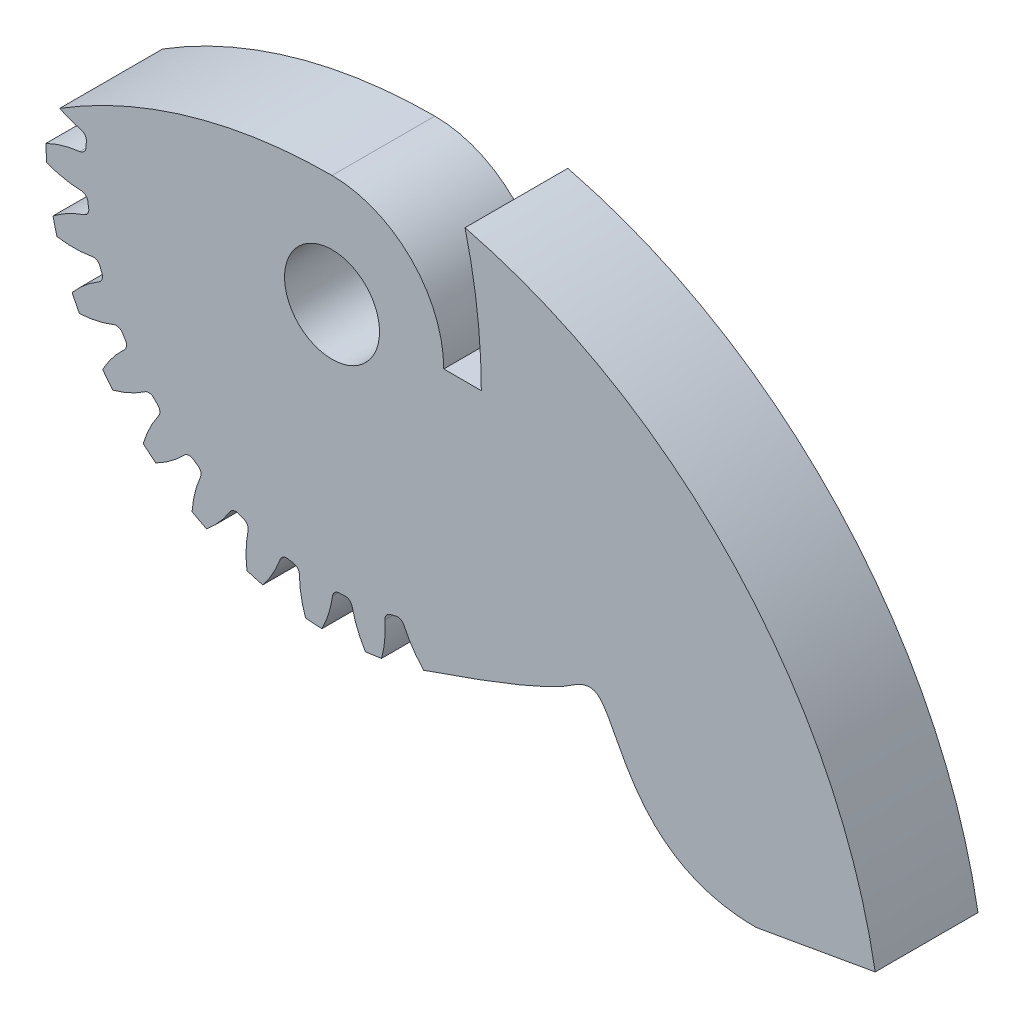
SolidWorks part; units mm, degrees
material "ABS"
ref_plane "Front" through (0, 0, 0) normal (0, 0, 1) x (1, 0, 0)
ref_plane "Top" through (0, 0, 0) normal (0, 1, 0) x (1, 0, 0)
ref_plane "Right" through (0, 0, 0) normal (1, 0, 0) x (0, 0, -1)
sketch "Sketch3" plane through (0, 0, 0) normal (0, 0, 1) x (1, 0, 0)
  circle A0 centre (0, 0) radius 40.64
  dimension "od" = 81.28
extrude "gearBody" add sketch "Sketch3" along normal blind 14.605
sketch "Sketch2" plane through (0, 0, 0) normal (0, 0, 1) x (1, 0, 0)
  line L0 (0, 0) -> (34.0786, 14.1158) construction
  line L1 (45.4751, -11.4855) -> (0, 0) construction
  line L2 (0, 0) -> (36.3143, 0) construction
  line L3 (38.0972, -0.458) -> (37.8451, -4.4001) construction
  line L5 (37.9712, -2.4291) -> (0, 0) construction
  line L7 (0, 0) -> (36.8864, 0) construction
  arc A0 (36.879, -0.7403) -> (36.6727, -3.9649) centre (0, 0) ccw construction
  arc A1 (40.637, 0.4947) -> (40.2427, -5.6687) centre (0, 0) ccw construction
  arc A2 (38.0972, -0.458) -> (37.8451, -4.4001) centre (0, 0) ccw construction
  arc A3 (34.9015, -2.6404) -> (34.9534, -1.8283) centre (0, 0) ccw
  arc A4 (45.4751, -11.4855) -> (35.6466, -3.6712) centre (32.0022, -18.3431) ccw
  arc A5 (45.4751, -11.4855) -> (46.5679, 5.5974) centre (0, 0) ccw
  arc A6 (46.5679, 5.5974) -> (35.8238, -0.9008) centre (34.0786, 14.1158) cw
  arc A7 (34.9534, -1.8283) -> (35.8238, -0.9008) centre (35.9376, -1.8798) cw
  arc A8 (35.6466, -3.6712) -> (34.9015, -2.6404) centre (35.8842, -2.7147) cw
  point P6 (46.5679, 5.5974)
  point P22 (45.4751, -11.4855)
  dimension "baseDia" = 73.7729
  dimension "od" = 81.28
  dimension "pd" = 76.2
  dimension "rd" = 70.0024
  dimension "rFillet" = 0.9855
  dimension "pointX" = 46.5679
  dimension "pointY" = 5.5974
  dimension "CTT" = 3.9421
  dimension "flankCenterAngle" = 22.5
extrude "toothCut" cut sketch "Sketch2" along normal through all
pattern_circular "CirPattern1" count 30 over 360 about axis through (0, 0, 14.605) along (0, 0, -1) of "toothCut"
sketch "hub1Dia" plane through (0, 0, 0) normal (0, 0, -1) x (-1, 0, 0)
  circle A0 centre (0, 0) radius 12.7
  dimension "hub1Dia" = 25.4
sketch "hub2Dia" plane through (0, 0, 14.605) normal (0, 0, 1) x (1, 0, 0)
  circle A0 centre (0, 0) radius 12.7
  dimension "hub2dia" = 25.4
sketch "boreDia" plane through (0, 0, 0) normal (0, 0, 1) x (1, 0, 0)
  circle A0 centre (0, 0) radius 6.7469
  dimension "boreDia" = 13.4937
extrude "bore" cut sketch "boreDia" against normal mid plane 25400
sketch "Sketch4" plane through (0, 0, 14.605) normal (0, 0, 1) x (1, 0, 0)
  circle A0 centre (0, -57.15) radius 78.359
  arc A2 (-42.9159, 8.4119) -> (42.9159, 8.4119) centre (0, 0) cw
  dimension "D1" = 156.718
  dimension "D2" = 57.15
extrude "Cut-Extrude1" cut sketch "Sketch4" against normal through all contours A0 region at (0, 27.8712, 14.605)
sketch "Sketch5" plane through (0, 0, 14.605) normal (0, 0, 1) x (1, 0, 0)
  line L0 (0, 21.209) -> (21.5163, 5.902)
  line L1 (21.5163, 5.902) -> (8.9608, -26.928)
  line L2 (8.9608, -26.928) -> (13.028, -38.4952)
  line L3 (0, 0) -> (0, -57.15) construction
  line L4 (0, -57.15) -> (-55.7146, -2.05) construction
  line L5 (0, -57.15) -> (67.8609, -96.3295) construction
  line L9 (0, -57.15) -> (77.1686, -43.5431) construction
  line L12 (60.232, -46.5295) -> (77.1686, -43.5431)
  line L13 (0, -57.15) -> (39.5947, -34.29) construction
  line L14 (39.5947, -34.29) -> (36.4197, -28.7907) construction
  circle A1 centre (0, -57.15) radius 78.359 construction
  arc A5 (0, 21.209) -> (77.1686, -43.5431) centre (0, -57.15) cw
  circle A6 centre (0, -57.15) radius 21.59 construction
  circle A12 centre (49.4934, -85.725) radius 40.64 construction
  spline S0 degree 3 poles (13.028, -38.4952) (34.3641, -31.2172) (33.2674, -29.3092) (40.5997, -27.9667) (42.6261, -46.4877) (60.232, -46.5295) knots 0 0 0 0 0.394503 0.494503 1 1 1 1
  point P10 (36.4197, -28.7907)
  point P16 (13.028, -38.6981)
  point P28 (21.569, -56.1981)
  dimension "D1" = 43.18
  dimension "D3" = 81.28
  dimension "D6" = 156.718
  dimension "D2" = 120
  dimension "D4" = 57.15
  dimension "D8" = 57.15
  dimension "D7" = 60
  dimension "D9" = 45.72
  dimension "D10" = 6.35
  dimension "D5" = 80
extrude "Boss-Extrude1" add sketch "Sketch5" against normal up to surface (14.605 mm away) up to face at (6.7469, 0, 0)
sketch "Sketch6" plane through (0, 0, 14.605) normal (0, 0, 1) x (1, 0, 0)
  line L1 (-41.2993, 3.0747) -> (-43.5539, 7.9898)
  line L2 (15.875, 0) -> (21.209, 0)
  circle A0 centre (0, -57.15) radius 78.359 construction
  arc A1 (77.1686, -43.5431) -> (-36.286, 12.3011) centre (0, -57.15) ccw construction
  circle A2 centre (0, 0) radius 15.875 construction
  arc A3 (0, 15.875) -> (15.875, 0) centre (0, 0) cw
  arc A4 (18.8964, 18.8964) -> (-43.5539, 7.9898) centre (0, -57.15) ccw
  arc A5 (0, 15.875) -> (-41.2993, 3.0747) centre (0, -57.15) ccw
  circle A6 centre (0, 0) radius 21.209 construction
  circle A8 centre (-57.15, 0) radius 78.359 construction
  arc A9 (21.209, 0) -> (18.8964, 18.8964) centre (-57.15, 0) ccw
  dimension "D4" = 57.15
  dimension "D1" = 31.75
  dimension "D2" = 42.418
  dimension "D3" = 156.718
extrude "Cut-Extrude2" cut sketch "Sketch6" against normal through all
equation "\"Bodytube_OD\" = 6.17in"
equation "\"Bodytube_ID\" = 5.998in"
equation "\"Fwd_Tube_Length\" = 40in"
equation "\"Mid_Tube_Length\" = 1in"
equation "\"Aft_Section_Length\"= 39in"
equation "\"Mid_Coupler_Length\"= 13in"
equation "\"Aft_Lower_Length\"= 22in"
equation "\"AB_Coupler_OD_Length\"= 1in"
equation "\"AB_Coupling_Section_Length\"= 0.375in"
equation "\"AB_Coupler_Length\"= \"AB_Coupler_OD_Length\" + \"AB_Coupling_Section_Length\" * 2"
equation "\"Cutout_Angle\" = 80"
equation "\"AB_Paddle_Height\" = 0.575in"
equation "\"AB_Coupler_Num_Screws\"= 6"
equation "\"Num_Cutouts\" = 3"
equation "\"AB_Coupler_OD\"= 6.17in"
equation "\"AB_Coupler_ID\"= 5.75in"
equation "\"AB_Coupler_Surface_Diameter\"= 5.998in"
equation "\"AB_Coupling_Screw_Diameter\"= 0.1065in"
equation "\"AB_Central_Bushing_Length\" = .75in"
equation "\"Lead_Screw_Dist\" = 2.25in"
equation "\"Lead_Screw_Diam\" = 11mm"
equation "\"Lead_Screw_Length\" = (\"Mid_Coupler_Length\" + 2*0.375in + 2*0.5in)"
equation "\"Paddle_Pin_Offset\" = .25in"
equation "\"Paddle_Pin_Radius\" = 2.25in"
equation "\"Fwd_BKHD_From_Top\" = 18in"
equation "\"D1@Sketch4\"=\"Bodytube_OD\""
equation "\"D2@Sketch4\"=\"Paddle_Pin_Radius\""
equation "\"D3@Sketch5\"=\"Paddle_Gear_OD\""
equation "\"D4@Sketch5\"=\"Paddle_Pin_Radius\""
equation "\"Motor_OD\" = 4in"
equation "\"Aft_Upper_Length\"= \"Aft_Section_Length\" - \"Aft_Lower_Length\" - \"AB_Coupler_OD_Length\""
equation "\"Paddle_Gear_OD\" = 3.2in"
equation "\"D5@Sketch5\"=\"Cutout_Angle\""
equation "\"D6@Sketch5\"=\"Bodytube_OD\""
equation "\"D1@Sketch6\"=\"AB_Coupler_ID\"-2*\"Paddle_Pin_Radius\""
equation "\"D2@Sketch6\"=\"Bodytube_OD\"-2*\"Paddle_Pin_Radius\""
equation "\"D3@Sketch6\"=\"Bodytube_OD\""
equation "\"D4@Sketch6\"=\"Paddle_Pin_Radius\""
equation "\"D8@Sketch5\"=\"Paddle_Pin_Radius\""
